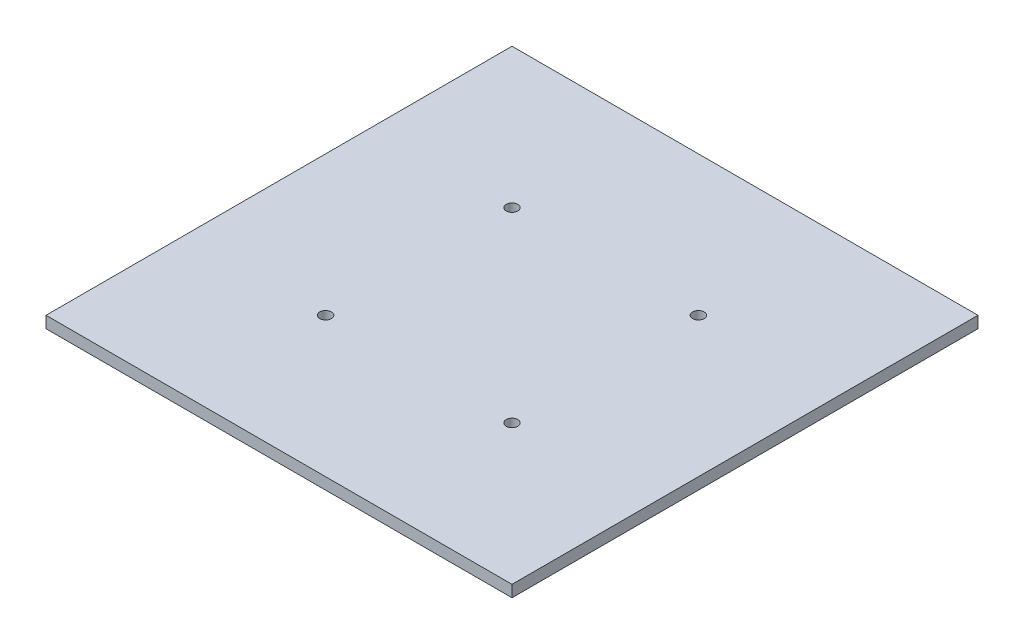
SolidWorks part; units mm, degrees
ref_plane "Front Plane" through (0, 0, 0) normal (0, 0, 1) x (1, 0, 0)
ref_plane "Top Plane" through (0, 0, 0) normal (0, 1, 0) x (1, 0, 0)
ref_plane "Right Plane" through (0, 0, 0) normal (1, 0, 0) x (0, 0, -1)
sketch "Sketch1" plane through (0, 0, 0) normal (0, 1, 0) x (1, 0, 0)
  line L0 (38.1, 0) -> (38.1, 127) construction
  line L1 (0, 0) -> (127, 0)
  line L2 (0, 0) -> (0, 127)
  line L3 (0, 127) -> (127, 127)
  line L4 (127, 0) -> (127, 127)
  line L5 (88.9, 127) -> (88.9, 0) construction
  line L6 (0, 38.1) -> (127, 38.1) construction
  line L7 (0, 88.9) -> (127, 88.9) construction
  circle A0 centre (38.1, 88.9) radius 1.5875
  circle A1 centre (88.9, 88.9) radius 1.5875
  circle A2 centre (38.1, 38.1) radius 1.5875
  circle A3 centre (88.9, 38.1) radius 1.5875
  dimension "D7" = 3.175
  dimension "D8" = 3.175
  dimension "D9" = 3.175
  dimension "D10" = 3.175
  dimension "D1" = 127
  dimension "D2" = 127
  dimension "D3" = 38.1
  dimension "D4" = 38.1
  dimension "D5" = 38.1
  dimension "D6" = 38.1
extrude "Boss-Extrude1" add sketch "Sketch1" along normal blind 3.175
